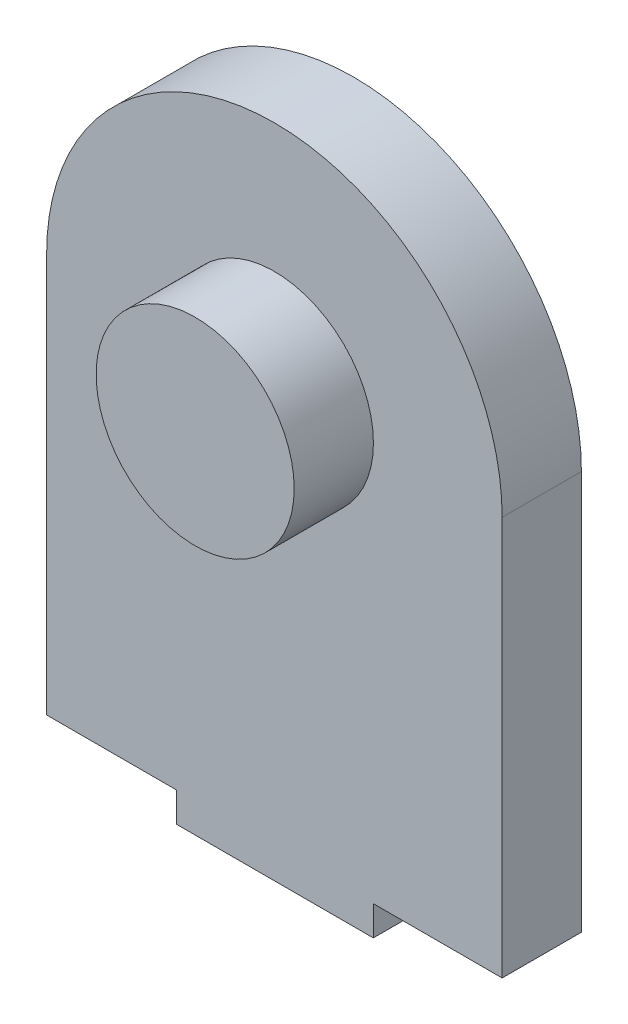
SolidWorks part; units mm, degrees
material "3d打印 35%"
ref_plane "前视基准面" through (0, 0, 0) normal (0, 0, 1) x (1, 0, 0)
ref_plane "上视基准面" through (0, 0, 0) normal (0, 1, 0) x (1, 0, 0)
ref_plane "右视基准面" through (0, 0, 0) normal (1, 0, 0) x (0, 0, -1)
sketch "草图1" plane through (0, 0, 0) normal (0, 0, 1) x (1, 0, 0)
  line L0 (-23, -40.29) -> (23, -40.29)
  line L5 (-23, -46) -> (23, 0) construction
  line L6 (-17.29, -5.71) -> (17.29, -40.29) construction
  line L8 (-23, -40.29) -> (-23, 0)
  line L10 (23, -40.29) -> (23, 0)
  line L11 (-23, -46) -> (23, 0) construction
  line L12 (-23, 0) -> (17.29, -40.29) construction
  circle A0 centre (0, 0) radius 23
  point P3 (0, -23)
  point P8 (0, -23)
  dimension "D1" = 46
extrude "凸台-拉伸1" add sketch "草图1" along normal blind 8 contours A0 | A0 | A0 region at (0, -28.5842, 0) region at (0, 0, 0)
sketch "草图2" plane through (0, 0, 8) normal (0, 0, 1) x (1, 0, 0)
  circle A0 centre (0, 0) radius 10
extrude "凸台-拉伸2" add sketch "草图2" along normal blind 8
ref_plane "基准面5" through (0, 0, 4) normal (0, 0, 1) x (1, 0, 0)
sketch "草图3" plane through (0, -40.29, 0) normal (0, -1, 0) x (-1, 0, 0)
  line L0 (-25.3, -4) -> (25.3, -4) construction
  line L1 (9.8593, 0) -> (-9.9912, 0)
  line L2 (9.8593, 0) -> (9.8593, -8)
  line L3 (9.8593, -8) -> (-9.9912, -8)
  line L4 (-9.9912, 0) -> (-9.9912, -8)
  line L5 (9.8593, 0) -> (-9.9912, -8) construction
  line L6 (9.8593, -8) -> (-9.9912, 0) construction
  line L7 (23, -8) -> (-23, -8) construction
  point P0 (-0.066, -4)
extrude "凸台-拉伸3" add sketch "草图3" along normal blind 3
ref_axis "基准轴1" through (-9.8593, -40.29, 4) along (-1, 0, 0)
sketch "草图4" plane through (0, -40.29, 0) normal (0, -1, 0) x (-1, 0, 0)
  line L0 (-25.3, -4) -> (25.3, -4) construction
  line L1 (23, -8) -> (23, 0) construction
  circle A0 centre (19, -4) radius 1.8
  dimension "D1" = 4
extrude "切除-拉伸1" cut sketch "草图4" against normal blind 5
ref_plane "基准面6" through (0, 0, 0) normal (-1, 0, 0) x (0, 0, 1)
mirror "镜向1" about plane through (0, 0, 0) normal (-1, 0, 0) of "切除-拉伸1"
